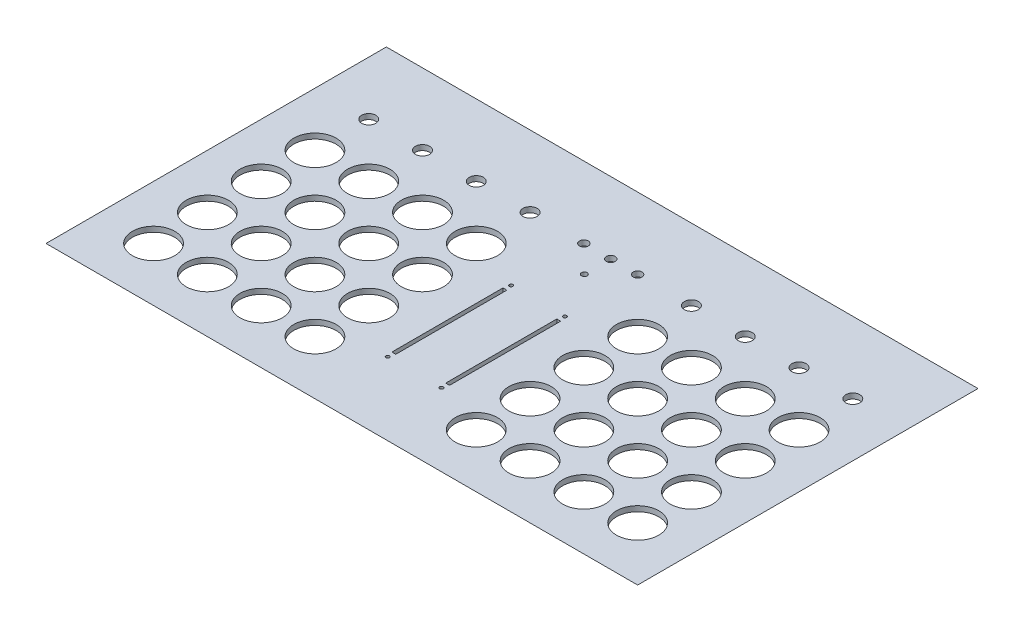
SolidWorks part; units mm, degrees
material "ABS"
ref_plane "Front Plane" through (0, 0, 0) normal (0, 0, 1) x (1, 0, 0)
ref_plane "Top Plane" through (0, 0, 0) normal (0, 1, 0) x (1, 0, 0)
ref_plane "Right Plane" through (0, 0, 0) normal (1, 0, 0) x (0, 0, -1)
sketch "Sketch2" plane through (0, 0, 0) normal (0, 1, 0) x (1, 0, 0)
  line L0 (0, 0) -> (91.5, 0) construction
  line L1 (0, 0) -> (0, 91.5) construction
  line L2 (122, 80.75) -> (122, 10.75) construction
  line L3 (120.9, 77.25) -> (123.1, 77.25)
  line L4 (120.9, 77.25) -> (120.9, 14.25)
  line L5 (120.9, 14.25) -> (123.1, 14.25)
  line L6 (123.1, 77.25) -> (123.1, 14.25)
  line L7 (91.5, 45.75) -> (137.25, 45.75) construction
  line L8 (91.5, 30.5) -> (91.5, 61) construction
  line L9 (0, 91.5) -> (0, 122) construction
  line L10 (0, 122) -> (91.5, 122) construction
  line L11 (0, 122) -> (30.5, 122) construction
  line L12 (137.25, -28.4189) -> (137.25, 162.5507) construction
  line L13 (274.5, 122) -> (244, 122) construction
  line L14 (274.5, 122) -> (183, 122) construction
  line L15 (274.5, 91.5) -> (274.5, 122) construction
  line L16 (183, 30.5) -> (183, 61) construction
  line L17 (152.5, 80.75) -> (152.5, 10.75) construction
  line L18 (274.5, 0) -> (274.5, 91.5) construction
  line L19 (274.5, 0) -> (183, 0) construction
  line L20 (151.4, 77.25) -> (151.4, 14.25)
  line L21 (153.6, 14.25) -> (151.4, 14.25)
  line L22 (153.6, 77.25) -> (153.6, 14.25)
  line L23 (153.6, 77.25) -> (151.4, 77.25)
  line L25 (-30.5, -30.5) -> (305, -30.5)
  line L26 (-30.5, -30.5) -> (-30.5, 162.5)
  line L27 (-30.5, 162.5) -> (305, 162.5)
  line L28 (305, -30.5) -> (305, 162.5)
  circle A0 centre (0, 0) radius 12
  circle A1 centre (30.5, 0) radius 12
  circle A2 centre (61, 0) radius 12
  circle A3 centre (91.5, 0) radius 12
  circle A4 centre (30.5, 30.5) radius 12
  circle A5 centre (61, 30.5) radius 12
  circle A6 centre (91.5, 30.5) radius 12
  circle A7 centre (30.5, 61) radius 12
  circle A8 centre (61, 61) radius 12
  circle A9 centre (91.5, 61) radius 12
  circle A10 centre (30.5, 91.5) radius 12
  circle A11 centre (61, 91.5) radius 12
  circle A12 centre (91.5, 91.5) radius 12
  circle A13 centre (0, 30.5) radius 12
  circle A14 centre (0, 61) radius 12
  circle A15 centre (0, 91.5) radius 12
  circle A16 centre (122, 80.75) radius 1
  circle A17 centre (122, 10.75) radius 1
  circle A18 centre (0, 122) radius 4
  circle A19 centre (30.5, 122) radius 4
  circle A20 centre (61, 122) radius 4
  circle A21 centre (91.5, 122) radius 4
  circle A22 centre (183, 122) radius 4
  circle A23 centre (213.5, 122) radius 4
  circle A24 centre (244, 122) radius 4
  circle A25 centre (274.5, 122) radius 4
  circle A26 centre (152.5, 10.75) radius 1
  circle A27 centre (152.5, 80.75) radius 1
  circle A28 centre (274.5, 91.5) radius 12
  circle A29 centre (274.5, 61) radius 12
  circle A30 centre (274.5, 30.5) radius 12
  circle A31 centre (183, 91.5) radius 12
  circle A32 centre (213.5, 91.5) radius 12
  circle A33 centre (244, 91.5) radius 12
  circle A34 centre (183, 61) radius 12
  circle A35 centre (213.5, 61) radius 12
  circle A36 centre (244, 61) radius 12
  circle A37 centre (183, 30.5) radius 12
  circle A38 centre (213.5, 30.5) radius 12
  circle A39 centre (244, 30.5) radius 12
  circle A40 centre (183, 0) radius 12
  circle A41 centre (213.5, 0) radius 12
  circle A42 centre (244, 0) radius 12
  circle A43 centre (274.5, 0) radius 12
  point P41 (122, 77.25)
  point P42 (120.9, 45.75)
  point P105 (153.6, 45.75)
  point P106 (152.5, 77.25)
  dimension "D1" = 24
  dimension "D8" = 2
  dimension "D12" = 8
  dimension "D4" = 30.5
  dimension "D5" = 30.5
  dimension "D6" = 63
  dimension "D7" = 2.2
  dimension "D9" = 3.5
  dimension "D10" = 3.5
  dimension "D11" = 30.5
  dimension "D14" = 30.5
  dimension "D15" = 30.5
  dimension "D16" = 15.25
  dimension "D17" = 30.5
  dimension "D18" = 30.5
  dimension "D19" = 30.5
  dimension "D20" = 40.5
  dimension "D2" = 4
  dimension "D3" = 4
  dimension "D13" = 4
extrude "Boss-Extrude1" add sketch "Sketch2" along normal blind 3
sketch "Sketch27" plane through (0, 3, 0) normal (0, 1, 0) x (1, 0, 0)
  line L0 (0, 122) -> (-6.364, 115.636) construction
  line L1 (-6.364, 115.636) -> (6.364, 115.636) construction
  line L2 (6.364, 115.636) -> (0, 122) construction
  line L3 (0, 131) -> (0, 135) construction
  line L4 (6.364, 115.636) -> (9.1924, 112.8076)
  line L5 (0, 122) -> (0.8429, 122.8429) construction
  line L6 (36.864, 115.636) -> (39.6924, 112.8076)
  line L7 (30.5, 122) -> (24.136, 115.636) construction
  line L8 (24.136, 115.636) -> (36.864, 115.636) construction
  line L9 (36.864, 115.636) -> (30.5, 122) construction
  line L10 (30.5, 131) -> (30.5, 135) construction
  line L11 (30.5, 122) -> (31.3429, 122.8429) construction
  line L12 (67.364, 115.636) -> (70.1924, 112.8076)
  line L13 (61, 122) -> (54.636, 115.636) construction
  line L14 (54.636, 115.636) -> (67.364, 115.636) construction
  line L15 (67.364, 115.636) -> (61, 122) construction
  line L16 (61, 131) -> (61, 135) construction
  line L17 (61, 122) -> (61.8429, 122.8429) construction
  line L18 (97.864, 115.636) -> (100.6924, 112.8076)
  line L19 (91.5, 122) -> (85.136, 115.636) construction
  line L20 (85.136, 115.636) -> (97.864, 115.636) construction
  line L21 (97.864, 115.636) -> (91.5, 122) construction
  line L22 (91.5, 131) -> (91.5, 135) construction
  line L23 (91.5, 122) -> (92.3429, 122.8429) construction
  line L24 (189.364, 115.636) -> (192.1924, 112.8076)
  line L25 (219.864, 115.636) -> (222.6924, 112.8076)
  line L26 (250.364, 115.636) -> (253.1924, 112.8076)
  line L27 (280.864, 115.636) -> (283.6924, 112.8076)
  line L28 (183, 122) -> (176.636, 115.636) construction
  line L29 (176.636, 115.636) -> (189.364, 115.636) construction
  line L30 (189.364, 115.636) -> (183, 122) construction
  line L31 (183, 131) -> (183, 135) construction
  line L32 (183, 122) -> (183.8429, 122.8429) construction
  line L33 (213.5, 122) -> (207.136, 115.636) construction
  line L34 (207.136, 115.636) -> (219.864, 115.636) construction
  line L35 (219.864, 115.636) -> (213.5, 122) construction
  line L36 (213.5, 131) -> (213.5, 135) construction
  line L37 (213.5, 122) -> (214.3429, 122.8429) construction
  line L38 (244, 122) -> (237.636, 115.636) construction
  line L39 (237.636, 115.636) -> (250.364, 115.636) construction
  line L40 (250.364, 115.636) -> (244, 122) construction
  line L41 (244, 131) -> (244, 135) construction
  line L42 (244, 122) -> (244.8429, 122.8429) construction
  line L43 (274.5, 122) -> (268.136, 115.636) construction
  line L44 (268.136, 115.636) -> (280.864, 115.636) construction
  line L45 (280.864, 115.636) -> (274.5, 122) construction
  line L46 (274.5, 131) -> (274.5, 135) construction
  line L47 (274.5, 122) -> (275.3429, 122.8429) construction
  line L48 (123.1, 14.25) -> (151.4, 14.25) construction
  line L49 (123.1, 77.25) -> (151.4, 77.25) construction
  line L50 (137.25, 14.25) -> (137.25, 77.25) construction
  line L51 (132.25, 15.25) -> (142.25, 15.25)
  line L52 (132.25, 14.25) -> (142.25, 14.25)
  line L53 (132.25, 47.25) -> (132.25, 48.25)
  line L54 (132.25, 14.25) -> (132.25, 15.25)
  line L55 (132.25, 15.25) -> (142.25, 15.25)
  line L56 (142.25, 14.25) -> (142.25, 15.25)
  line L57 (132.25, 16.25) -> (142.25, 16.25)
  line L58 (142.25, 47.25) -> (142.25, 48.25)
  line L59 (132.25, 16.25) -> (142.25, 16.25)
  line L60 (132.25, 16.25) -> (132.25, 17.25)
  line L61 (132.25, 77.25) -> (132.25, 78.25)
  line L62 (142.25, 16.25) -> (142.25, 17.25)
  line L63 (132.25, 78.25) -> (142.25, 78.25)
  line L64 (132.25, 17.25) -> (132.25, 18.25)
  line L65 (132.25, 18.25) -> (142.25, 18.25)
  line L66 (142.25, 17.25) -> (142.25, 18.25)
  line L67 (132.25, 18.25) -> (142.25, 18.25)
  line L68 (142.25, 78.25) -> (142.25, 77.25)
  line L69 (132.25, 19.25) -> (142.25, 19.25)
  line L71 (132.25, 19.25) -> (142.25, 19.25)
  line L72 (132.25, 19.25) -> (132.25, 20.25)
  line L74 (142.25, 19.25) -> (142.25, 20.25)
  line L76 (132.25, 20.25) -> (132.25, 21.25)
  line L78 (142.25, 20.25) -> (142.25, 21.25)
  line L80 (132.25, 21.25) -> (132.25, 22.25)
  line L81 (132.25, 22.25) -> (142.25, 22.25)
  line L82 (142.25, 21.25) -> (142.25, 22.25)
  line L83 (132.25, 22.25) -> (142.25, 22.25)
  line L85 (132.25, 23.25) -> (142.25, 23.25)
  line L87 (132.25, 23.25) -> (142.25, 23.25)
  line L88 (132.25, 23.25) -> (132.25, 24.25)
  line L90 (142.25, 23.25) -> (142.25, 24.25)
  line L92 (132.25, 24.25) -> (132.25, 25.25)
  line L94 (142.25, 24.25) -> (142.25, 25.25)
  line L96 (132.25, 25.25) -> (132.25, 26.25)
  line L98 (142.25, 25.25) -> (142.25, 26.25)
  line L100 (132.25, 26.25) -> (132.25, 27.25)
  line L101 (132.25, 27.25) -> (142.25, 27.25)
  line L102 (142.25, 26.25) -> (142.25, 27.25)
  line L103 (132.25, 27.25) -> (142.25, 27.25)
  line L105 (132.25, 28.25) -> (142.25, 28.25)
  line L107 (132.25, 28.25) -> (142.25, 28.25)
  line L108 (132.25, 28.25) -> (132.25, 29.25)
  line L110 (142.25, 28.25) -> (142.25, 29.25)
  line L112 (132.25, 29.25) -> (132.25, 30.25)
  line L114 (142.25, 29.25) -> (142.25, 30.25)
  line L116 (132.25, 30.25) -> (132.25, 31.25)
  line L118 (142.25, 30.25) -> (142.25, 31.25)
  line L120 (132.25, 31.25) -> (132.25, 32.25)
  line L122 (142.25, 31.25) -> (142.25, 32.25)
  line L124 (132.25, 32.25) -> (132.25, 33.25)
  line L125 (132.25, 33.25) -> (142.25, 33.25)
  line L126 (142.25, 32.25) -> (142.25, 33.25)
  line L127 (132.25, 33.25) -> (142.25, 33.25)
  line L129 (132.25, 34.25) -> (142.25, 34.25)
  line L131 (132.25, 34.25) -> (142.25, 34.25)
  line L132 (132.25, 34.25) -> (132.25, 35.25)
  line L134 (142.25, 34.25) -> (142.25, 35.25)
  line L136 (132.25, 35.25) -> (132.25, 36.25)
  line L138 (142.25, 35.25) -> (142.25, 36.25)
  line L140 (132.25, 36.25) -> (132.25, 37.25)
  line L142 (142.25, 36.25) -> (142.25, 37.25)
  line L144 (132.25, 37.25) -> (132.25, 38.25)
  line L146 (142.25, 37.25) -> (142.25, 38.25)
  line L148 (132.25, 38.25) -> (132.25, 39.25)
  line L150 (142.25, 38.25) -> (142.25, 39.25)
  line L152 (132.25, 39.25) -> (132.25, 40.25)
  line L153 (132.25, 40.25) -> (142.25, 40.25)
  line L154 (142.25, 39.25) -> (142.25, 40.25)
  line L155 (132.25, 40.25) -> (142.25, 40.25)
  line L157 (132.25, 41.25) -> (142.25, 41.25)
  line L159 (132.25, 41.25) -> (142.25, 41.25)
  line L160 (132.25, 41.25) -> (132.25, 42.25)
  line L162 (142.25, 41.25) -> (142.25, 42.25)
  line L164 (132.25, 42.25) -> (132.25, 43.25)
  line L166 (142.25, 42.25) -> (142.25, 43.25)
  line L168 (132.25, 43.25) -> (132.25, 44.25)
  line L170 (142.25, 43.25) -> (142.25, 44.25)
  line L172 (132.25, 44.25) -> (132.25, 45.25)
  line L174 (142.25, 44.25) -> (142.25, 45.25)
  line L176 (132.25, 45.25) -> (132.25, 46.25)
  line L178 (142.25, 45.25) -> (142.25, 46.25)
  line L180 (132.25, 46.25) -> (132.25, 47.25)
  line L182 (142.25, 46.25) -> (142.25, 47.25)
  line L185 (132.25, 48.25) -> (142.25, 48.25)
  line L187 (132.25, 48.25) -> (142.25, 48.25)
  line L189 (132.25, 49.25) -> (142.25, 49.25)
  line L191 (132.25, 49.25) -> (142.25, 49.25)
  line L192 (132.25, 49.25) -> (132.25, 50.25)
  line L194 (142.25, 49.25) -> (142.25, 50.25)
  line L196 (132.25, 50.25) -> (132.25, 51.25)
  line L198 (142.25, 50.25) -> (142.25, 51.25)
  line L200 (132.25, 51.25) -> (132.25, 52.25)
  line L202 (142.25, 51.25) -> (142.25, 52.25)
  line L204 (132.25, 52.25) -> (132.25, 53.25)
  line L206 (142.25, 52.25) -> (142.25, 53.25)
  line L208 (132.25, 53.25) -> (132.25, 54.25)
  line L210 (142.25, 53.25) -> (142.25, 54.25)
  line L212 (132.25, 54.25) -> (132.25, 55.25)
  line L214 (142.25, 54.25) -> (142.25, 55.25)
  line L216 (132.25, 55.25) -> (132.25, 56.25)
  line L218 (142.25, 55.25) -> (142.25, 56.25)
  line L220 (132.25, 56.25) -> (132.25, 57.25)
  line L221 (132.25, 57.25) -> (142.25, 57.25)
  line L222 (142.25, 56.25) -> (142.25, 57.25)
  line L223 (132.25, 57.25) -> (142.25, 57.25)
  line L225 (132.25, 58.25) -> (142.25, 58.25)
  line L227 (132.25, 58.25) -> (142.25, 58.25)
  line L228 (132.25, 58.25) -> (132.25, 59.25)
  line L230 (142.25, 58.25) -> (142.25, 59.25)
  line L232 (132.25, 59.25) -> (132.25, 60.25)
  line L234 (142.25, 59.25) -> (142.25, 60.25)
  line L236 (132.25, 60.25) -> (132.25, 61.25)
  line L238 (142.25, 60.25) -> (142.25, 61.25)
  line L240 (132.25, 61.25) -> (132.25, 62.25)
  line L242 (142.25, 61.25) -> (142.25, 62.25)
  line L244 (132.25, 62.25) -> (132.25, 63.25)
  line L246 (142.25, 62.25) -> (142.25, 63.25)
  line L248 (132.25, 63.25) -> (132.25, 64.25)
  line L250 (142.25, 63.25) -> (142.25, 64.25)
  line L252 (132.25, 64.25) -> (132.25, 65.25)
  line L254 (142.25, 64.25) -> (142.25, 65.25)
  line L256 (132.25, 65.25) -> (132.25, 66.25)
  line L258 (142.25, 65.25) -> (142.25, 66.25)
  line L260 (132.25, 66.25) -> (132.25, 67.25)
  line L261 (132.25, 67.25) -> (142.25, 67.25)
  line L262 (142.25, 66.25) -> (142.25, 67.25)
  line L263 (132.25, 67.25) -> (142.25, 67.25)
  line L265 (132.25, 68.25) -> (142.25, 68.25)
  line L267 (132.25, 68.25) -> (142.25, 68.25)
  line L268 (132.25, 68.25) -> (132.25, 69.25)
  line L270 (142.25, 68.25) -> (142.25, 69.25)
  line L272 (132.25, 69.25) -> (132.25, 70.25)
  line L274 (142.25, 69.25) -> (142.25, 70.25)
  line L276 (132.25, 70.25) -> (132.25, 71.25)
  line L278 (142.25, 70.25) -> (142.25, 71.25)
  line L280 (132.25, 71.25) -> (132.25, 72.25)
  line L282 (142.25, 71.25) -> (142.25, 72.25)
  line L284 (132.25, 72.25) -> (132.25, 73.25)
  line L286 (142.25, 72.25) -> (142.25, 73.25)
  line L288 (132.25, 73.25) -> (132.25, 74.25)
  line L290 (142.25, 73.25) -> (142.25, 74.25)
  line L292 (132.25, 74.25) -> (132.25, 75.25)
  line L294 (142.25, 74.25) -> (142.25, 75.25)
  line L296 (132.25, 75.25) -> (132.25, 76.25)
  line L298 (142.25, 75.25) -> (142.25, 76.25)
  line L300 (132.25, 76.25) -> (132.25, 77.25)
  line L302 (142.25, 76.25) -> (142.25, 77.25)
  line L303 (142.25, 15.25) -> (142.25, 16.25)
  line L304 (132.25, 15.25) -> (132.25, 16.25)
  line L305 (137.25, 17.25) -> (142.25, 17.25)
  line L306 (137.25, 17.25) -> (142.25, 17.25)
  line L307 (132.25, 18.25) -> (132.25, 19.25)
  line L308 (142.25, 18.25) -> (142.25, 19.25)
  line L309 (132.25, 20.25) -> (137.25, 20.25)
  line L310 (132.25, 20.25) -> (137.25, 20.25)
  line L311 (132.25, 21.25) -> (137.25, 21.25)
  line L312 (132.25, 21.25) -> (137.25, 21.25)
  line L313 (132.25, 22.25) -> (132.25, 23.25)
  line L314 (142.25, 22.25) -> (142.25, 23.25)
  line L315 (132.25, 24.25) -> (137.25, 24.25)
  line L316 (132.25, 24.25) -> (137.25, 24.25)
  line L317 (132.25, 25.25) -> (137.25, 25.25)
  line L318 (132.25, 25.25) -> (137.25, 25.25)
  line L319 (132.25, 26.25) -> (137.25, 26.25)
  line L320 (132.25, 26.25) -> (137.25, 26.25)
  line L321 (132.25, 27.25) -> (132.25, 28.25)
  line L322 (142.25, 27.25) -> (142.25, 28.25)
  line L323 (132.25, 32.25) -> (137.25, 32.25)
  line L324 (132.25, 32.25) -> (137.25, 32.25)
  line L325 (132.25, 31.25) -> (137.25, 31.25)
  line L326 (132.25, 31.25) -> (137.25, 31.25)
  line L327 (132.25, 30.25) -> (137.25, 30.25)
  line L328 (132.25, 30.25) -> (137.25, 30.25)
  line L329 (132.25, 29.25) -> (137.25, 29.25)
  line L330 (132.25, 29.25) -> (137.25, 29.25)
  line L331 (132.25, 33.25) -> (132.25, 34.25)
  line L332 (142.25, 33.25) -> (142.25, 34.25)
  line L333 (132.25, 35.25) -> (137.25, 35.25)
  line L334 (132.25, 35.25) -> (137.25, 35.25)
  line L335 (132.25, 36.25) -> (137.25, 36.25)
  line L336 (132.25, 36.25) -> (137.25, 36.25)
  line L337 (132.25, 37.25) -> (137.25, 37.25)
  line L338 (132.25, 37.25) -> (137.25, 37.25)
  line L339 (132.25, 38.25) -> (137.25, 38.25)
  line L340 (132.25, 38.25) -> (137.25, 38.25)
  line L341 (132.25, 39.25) -> (137.25, 39.25)
  line L342 (132.25, 39.25) -> (137.25, 39.25)
  line L343 (132.25, 40.25) -> (132.25, 41.25)
  line L344 (142.25, 40.25) -> (142.25, 41.25)
  line L345 (132.25, 43.25) -> (137.25, 43.25)
  line L346 (132.25, 43.25) -> (137.25, 43.25)
  line L347 (132.25, 42.25) -> (137.25, 42.25)
  line L348 (132.25, 42.25) -> (137.25, 42.25)
  line L349 (132.25, 44.25) -> (137.25, 44.25)
  line L350 (132.25, 44.25) -> (137.25, 44.25)
  line L351 (132.25, 45.25) -> (137.25, 45.25)
  line L352 (132.25, 45.25) -> (137.25, 45.25)
  line L353 (132.25, 46.25) -> (137.25, 46.25)
  line L354 (132.25, 46.25) -> (137.25, 46.25)
  line L355 (132.25, 47.25) -> (132.25, 48.25)
  line L356 (142.25, 47.25) -> (142.25, 48.25)
  line L357 (142.25, 48.25) -> (142.25, 49.25)
  line L358 (132.25, 48.25) -> (132.25, 49.25)
  line L359 (137.25, 47.25) -> (142.25, 47.25)
  line L360 (137.25, 47.25) -> (142.25, 47.25)
  line L361 (132.25, 51.25) -> (137.25, 51.25)
  line L362 (132.25, 51.25) -> (137.25, 51.25)
  line L363 (132.25, 50.25) -> (137.25, 50.25)
  line L364 (132.25, 50.25) -> (137.25, 50.25)
  line L365 (132.25, 52.25) -> (137.25, 52.25)
  line L366 (132.25, 52.25) -> (137.25, 52.25)
  line L367 (132.25, 53.25) -> (137.25, 53.25)
  line L368 (132.25, 53.25) -> (137.25, 53.25)
  line L369 (132.25, 54.25) -> (137.25, 54.25)
  line L370 (132.25, 54.25) -> (137.25, 54.25)
  line L371 (132.25, 55.25) -> (137.25, 55.25)
  line L372 (132.25, 55.25) -> (137.25, 55.25)
  line L373 (132.25, 56.25) -> (137.25, 56.25)
  line L374 (132.25, 56.25) -> (137.25, 56.25)
  line L375 (142.25, 57.25) -> (142.25, 58.25)
  line L376 (132.25, 57.25) -> (132.25, 58.25)
  line L377 (137.25, 60.25) -> (142.25, 60.25)
  line L378 (137.25, 60.25) -> (142.25, 60.25)
  line L379 (137.25, 61.25) -> (142.25, 61.25)
  line L380 (137.25, 61.25) -> (142.25, 61.25)
  line L381 (137.25, 62.25) -> (142.25, 62.25)
  line L382 (137.25, 62.25) -> (142.25, 62.25)
  line L383 (137.25, 63.25) -> (142.25, 63.25)
  line L384 (137.25, 63.25) -> (142.25, 63.25)
  line L385 (137.25, 64.25) -> (142.25, 64.25)
  line L386 (137.25, 64.25) -> (142.25, 64.25)
  line L387 (137.25, 65.25) -> (142.25, 65.25)
  line L388 (137.25, 65.25) -> (142.25, 65.25)
  line L389 (137.25, 66.25) -> (142.25, 66.25)
  line L390 (137.25, 66.25) -> (142.25, 66.25)
  line L391 (140.5009, 59.25) -> (142.25, 59.25)
  line L392 (140.5009, 59.25) -> (142.25, 59.25)
  line L393 (142.25, 67.25) -> (142.25, 68.25)
  line L394 (132.25, 67.25) -> (132.25, 68.25)
  line L395 (137.25, 69.25) -> (142.25, 69.25)
  line L396 (137.25, 69.25) -> (142.25, 69.25)
  line L397 (137.25, 70.25) -> (142.25, 70.25)
  line L398 (137.25, 70.25) -> (142.25, 70.25)
  line L399 (137.25, 71.25) -> (142.25, 71.25)
  line L400 (137.25, 71.25) -> (142.25, 71.25)
  line L401 (137.25, 72.25) -> (142.25, 72.25)
  line L402 (137.25, 72.25) -> (142.25, 72.25)
  line L403 (137.25, 73.25) -> (142.25, 73.25)
  line L404 (137.25, 73.25) -> (142.25, 73.25)
  line L405 (137.25, 74.25) -> (142.25, 74.25)
  line L406 (137.25, 74.25) -> (142.25, 74.25)
  line L407 (137.25, 75.25) -> (142.25, 75.25)
  line L408 (137.25, 75.25) -> (142.25, 75.25)
  line L409 (137.25, 76.25) -> (142.25, 76.25)
  line L410 (137.25, 76.25) -> (142.25, 76.25)
  line L411 (132.25, 77.25) -> (142.25, 77.25)
  arc A0 (6.364, 115.636) -> (-8.8817, 120.5456) centre (0, 122) ccw
  arc A1 (9.1924, 112.8076) -> (0, 135) centre (0, 122) ccw construction
  arc A2 (0, 133) -> (-9.0777, 120.5065) centre (0.8429, 122.8429) ccw
  arc A3 (9.1924, 112.8076) -> (0, 133) centre (0.8167, 121.1833) ccw
  arc A4 (36.864, 115.636) -> (21.6183, 120.5456) centre (30.5, 122) ccw
  arc A5 (39.6924, 112.8076) -> (30.5, 135) centre (30.5, 122) ccw construction
  arc A6 (30.5, 133) -> (21.4223, 120.5065) centre (31.3429, 122.8429) ccw
  arc A7 (39.6924, 112.8076) -> (30.5, 133) centre (31.3167, 121.1833) ccw
  arc A8 (67.364, 115.636) -> (52.1183, 120.5456) centre (61, 122) ccw
  arc A9 (70.1924, 112.8076) -> (61, 135) centre (61, 122) ccw construction
  arc A10 (61, 133) -> (51.9223, 120.5065) centre (61.8429, 122.8429) ccw
  arc A11 (70.1924, 112.8076) -> (61, 133) centre (61.8167, 121.1833) ccw
  arc A12 (97.864, 115.636) -> (82.6183, 120.5456) centre (91.5, 122) ccw
  arc A13 (100.6924, 112.8076) -> (91.5, 135) centre (91.5, 122) ccw construction
  arc A14 (91.5, 133) -> (82.4223, 120.5065) centre (92.3429, 122.8429) ccw
  arc A15 (100.6924, 112.8076) -> (91.5, 133) centre (92.3167, 121.1833) ccw
  arc A16 (189.364, 115.636) -> (174.1183, 120.5456) centre (183, 122) ccw
  arc A17 (183, 133) -> (173.9223, 120.5065) centre (183.8429, 122.8429) ccw
  arc A18 (192.1924, 112.8076) -> (183, 133) centre (183.8167, 121.1833) ccw
  arc A19 (219.864, 115.636) -> (204.6183, 120.5456) centre (213.5, 122) ccw
  arc A20 (213.5, 133) -> (204.4223, 120.5065) centre (214.3429, 122.8429) ccw
  arc A21 (222.6924, 112.8076) -> (213.5, 133) centre (214.3167, 121.1833) ccw
  arc A22 (250.364, 115.636) -> (235.1183, 120.5456) centre (244, 122) ccw
  arc A23 (244, 133) -> (234.9223, 120.5065) centre (244.8429, 122.8429) ccw
  arc A24 (253.1924, 112.8076) -> (244, 133) centre (244.8167, 121.1833) ccw
  arc A25 (280.864, 115.636) -> (265.6183, 120.5456) centre (274.5, 122) ccw
  arc A26 (274.5, 133) -> (265.4223, 120.5065) centre (275.3429, 122.8429) ccw
  arc A27 (283.6924, 112.8076) -> (274.5, 133) centre (275.3167, 121.1833) ccw
  arc A28 (192.1924, 112.8076) -> (183, 135) centre (183, 122) ccw construction
  arc A29 (222.6924, 112.8076) -> (213.5, 135) centre (213.5, 122) ccw construction
  arc A30 (253.1924, 112.8076) -> (244, 135) centre (244, 122) ccw construction
  arc A31 (283.6924, 112.8076) -> (274.5, 135) centre (274.5, 122) ccw construction
  arc A32 (265.6183, 120.5456) -> (265.4223, 120.5065) centre (265.5196, 120.5294) cw
  arc A33 (235.1183, 120.5456) -> (234.9223, 120.5065) centre (235.0196, 120.5294) cw
  arc A34 (204.6183, 120.5456) -> (204.4223, 120.5065) centre (204.5196, 120.5294) cw
  arc A35 (174.1183, 120.5456) -> (173.9223, 120.5065) centre (174.0196, 120.5294) cw
  arc A36 (82.6183, 120.5456) -> (82.4223, 120.5065) centre (82.5196, 120.5294) cw
  arc A37 (52.1183, 120.5456) -> (51.9223, 120.5065) centre (52.0196, 120.5294) cw
  arc A38 (21.6183, 120.5456) -> (21.4223, 120.5065) centre (21.5196, 120.5294) cw
  arc A39 (-9.0777, 120.5065) -> (-8.8817, 120.5456) centre (-8.9804, 120.5294) ccw
  point P11 (0, 133)
  point P20 (30.5, 133)
  point P30 (61, 133)
  point P40 (91.5, 133)
  point P50 (183, 133)
  point P59 (213.5, 133)
  point P69 (244, 133)
  point P79 (274.5, 133)
  point P95 (137.25, 14.25)
  point P102 (137.25, 15.25)
  point P107 (137.25, 16.25)
  point P112 (137.25, 17.25)
  point P117 (137.25, 18.25)
  point P122 (137.25, 19.25)
  point P127 (137.25, 20.25)
  point P132 (137.25, 21.25)
  point P137 (137.25, 22.25)
  point P142 (137.25, 23.25)
  point P147 (137.25, 24.25)
  point P152 (137.25, 25.25)
  point P157 (137.25, 26.25)
  point P162 (137.25, 27.25)
  point P167 (137.25, 28.25)
  point P172 (137.25, 29.25)
  point P177 (137.25, 30.25)
  point P182 (137.25, 31.25)
  point P187 (137.25, 32.25)
  point P192 (137.25, 33.25)
  point P197 (137.25, 34.25)
  point P202 (137.25, 35.25)
  point P207 (137.25, 36.25)
  point P212 (137.25, 37.25)
  point P217 (137.25, 38.25)
  point P222 (137.25, 39.25)
  point P227 (137.25, 40.25)
  point P232 (137.25, 41.25)
  point P237 (137.25, 42.25)
  point P242 (137.25, 43.25)
  point P247 (137.25, 44.25)
  point P252 (137.25, 45.25)
  point P257 (137.25, 46.25)
  point P262 (137.25, 47.25)
  point P267 (137.25, 48.25)
  point P272 (137.25, 49.25)
  point P277 (137.25, 50.25)
  point P282 (137.25, 51.25)
  point P287 (137.25, 52.25)
  point P292 (137.25, 53.25)
  point P297 (137.25, 54.25)
  point P302 (137.25, 55.25)
  point P307 (137.25, 56.25)
  point P312 (137.25, 57.25)
  point P317 (137.25, 58.25)
  point P322 (137.25, 59.25)
  point P327 (137.25, 60.25)
  point P332 (137.25, 61.25)
  point P337 (137.25, 62.25)
  point P342 (137.25, 63.25)
  point P347 (137.25, 64.25)
  point P352 (137.25, 65.25)
  point P357 (137.25, 66.25)
  point P362 (137.25, 67.25)
  point P367 (137.25, 68.25)
  point P372 (137.25, 69.25)
  point P377 (137.25, 70.25)
  point P382 (137.25, 71.25)
  point P387 (137.25, 72.25)
  point P392 (137.25, 73.25)
  point P397 (137.25, 74.25)
  point P402 (137.25, 75.25)
  point P407 (137.25, 76.25)
  dimension "D1" = 18
  dimension "D3" = 26
  dimension "D10" = 0.1
  dimension "D2" = 270
  dimension "D6" = 10
  dimension "D7" = 1
  dimension "D8" = 63
  dimension "D9" = 1
  dimension "D4" = 4
  dimension "D5" = 2
extrude "Cut-Extrude14" [suppressed] cut sketch "Sketch27" against normal blind 0.2 contours L6 A7 A6 A4 | L24 A18 A17 A16 | L25 A21 A20 A19 | L26 A24 A23 A22 | L27 A27 A26 A25 | L52 L56 L51 L54 | L62 L66 L65 L64 L60 L57 | L78 L82 L81 L80 L76 L72 L69 L74 | L98 L102 L101 L100 L96 L92 L88 L85 L90 L94 | L122 L126 L125 L124 L120 L116 L112 L108 L105 L110 L114 L118 | L150 L154 L153 L152 L148 L144 L140 L136 L132 L129 L134 L138 L142 L146 | L298 L302 L68 L63 L61 L300 L296 L292 L288 L284 L280 L276 L272 L268 L265 L270 L274 L278 L282 L286 L290 L294 | L258 L262 L261 L260 L256 L252 L248 L244 L240 L236 L232 L228 L225 L230 L234 L238 L242 L246 L250 L254 | L218 L222 L221 L220 L216 L212 L208 L204 L200 L196 L192 L189 L194 L198 L202 L206 L210 L214 | L185 L53 L180 L176 L172 L168 L164 L160 L157 L162 L166 L170 L174 L178 L182 L58 | A0 A39 A2 A3 L4 | A8 A37 A10 A11 L12 | A12 A36 A14 A15 L18
sketch "Sketch3" plane through (0, 3, 0) normal (0, 1, 0) x (1, 0, 0)
  line L0 (91.5, 122) -> (183, 122) construction
  line L1 (137.25, 160.5) -> (137.25, 122) construction
  line L3 (122, 80.75) -> (122, 122) construction
  line L4 (152.5, 122) -> (152.5, 80.75) construction
  line L5 (137.25, 122) -> (137.25, 107) construction
  circle A0 centre (122, 122) radius 2.5
  circle A1 centre (137.25, 122) radius 2.5
  circle A2 centre (152.5, 122) radius 2.5
  circle A3 centre (137.25, 107) radius 1.6
  dimension "D1" = 5
  dimension "D2" = 3.2
  dimension "D3" = 15
extrude "Cut-Extrude1" cut sketch "Sketch3" against normal blind 10
chamfer "Chamfer2" distance 3 angle 45 4 edges at (-30.5, 0, -66) (137.25, 0, 30.5) (305, 0, -66) (137.25, 0, -162.5)
